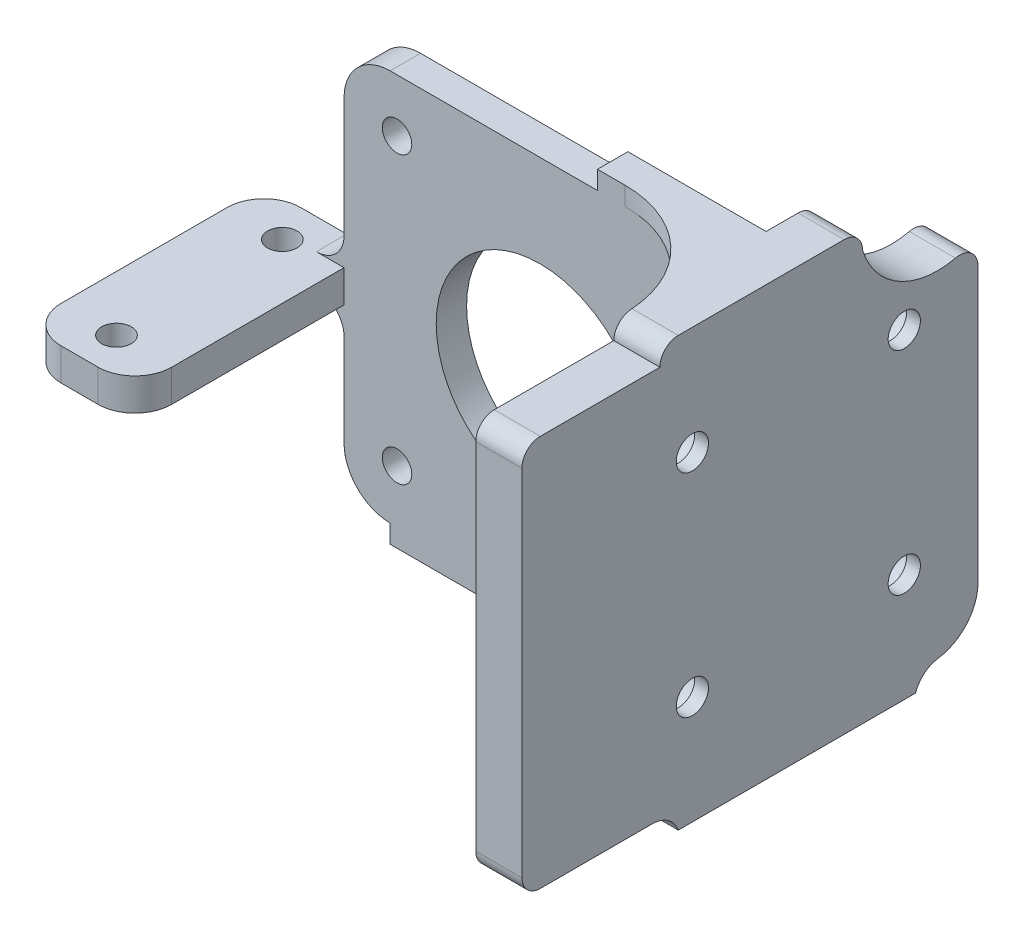
SolidWorks part; units mm, degrees
ref_plane "Alzado" through (0, 0, 0) normal (0, 0, 1) x (1, 0, 0)
ref_plane "Planta" through (0, 0, 0) normal (0, 1, 0) x (1, 0, 0)
ref_plane "Vista lateral" through (0, 0, 0) normal (1, 0, 0) x (0, 0, -1)
sketch "Croquis1" plane through (0, 0, 0) normal (1, 0, 0) x (0, 0, -1)
  line L1 (-23.5797, 14.1196) -> (18.9203, 14.1196)
  line L2 (-23.5797, 14.1196) -> (-23.5797, -28.3804)
  line L3 (-23.5797, -28.3804) -> (18.9203, -28.3804)
  line L4 (18.9203, 14.1196) -> (18.9203, -28.3804)
  dimension "D1" = 42.5
  dimension "D2" = 42.5
extrude "Saliente-Extruir1" add sketch "Croquis1" against normal blind 5
sketch "Croquis6" plane through (0, 0, -18.9203) normal (0, 0, -1) x (-1, 0, 0)
  line L4 (0, 14.1196) -> (0, -28.3804)
  line L5 (0, -28.3804) -> (5, -28.3804)
  line L6 (5, -28.3804) -> (5, 14.1196)
  line L7 (5, 14.1196) -> (0, 14.1196)
  line L8 (0, 14.1196) -> (0, -28.3804)
  line L9 (0, -28.3804) -> (5, -28.3804)
  line L10 (5, -28.3804) -> (5, 14.1196)
  line L11 (5, 14.1196) -> (0, 14.1196)
  dimension "D1" = 0
extrude "Saliente-Extruir2" add sketch "Croquis6" along normal blind 4
sketch "Croquis7" plane through (-5, 0, 0) normal (-1, 0, 0) x (0, 0, 1)
  line L0 (23.5797, -28.3804) -> (-22.9203, -28.3804) construction
  line L1 (-22.9203, 14.1196) -> (-18.9203, 14.1196)
  line L2 (-22.9203, 14.1196) -> (-22.9203, -28.3804)
  line L3 (-22.9203, -28.3804) -> (-18.9203, -28.3804)
  line L4 (-18.9203, 14.1196) -> (-18.9203, -28.3804)
  dimension "D1" = 4
extrude "Saliente-Extruir3" add sketch "Croquis7" along normal blind 42.5
sketch "Croquis8" plane through (0, 0, -18.9203) normal (0, 0, 1) x (1, 0, 0)
  line L0 (-47.5, 14.1196) -> (-41.75, 8.3696) construction
  line L1 (-47.5, -28.3804) -> (-41.75, -22.6304) construction
  line L2 (-40.6186, 7.2382) -> (-11.8814, -21.499) construction
  line L5 (-40.6186, -21.499) -> (-11.8814, 7.2382) construction
  line L7 (-40.6186, -21.499) -> (-11.8814, 7.2382) construction
  line L8 (-40.6186, 7.2382) -> (-11.8814, -21.499) construction
  line L9 (-10.75, 8.3696) -> (-5, 14.1196) construction
  line L10 (-10.75, -22.6304) -> (-5, -28.3804) construction
  circle A0 centre (-26.25, -7.1304) radius 11.25
  circle A1 centre (-41.75, 8.3696) radius 1.6
  circle A2 centre (-10.75, 8.3696) radius 1.6
  circle A3 centre (-10.75, -22.6304) radius 1.6
  circle A4 centre (-41.75, -22.6304) radius 1.6
  dimension "D1" = 22.5
  dimension "D4" = 31
  dimension "D2" = 31
  dimension "D3" = 31
extrude "Cortar-Extruir2" cut sketch "Croquis8" against normal blind 4
sketch "Croquis10" plane through (-47.5, 0, 0) normal (-1, 0, 0) x (0, 0, 1)
  line L0 (-18.9203, -28.3804) -> (-18.9203, 14.1196) construction
  line L1 (-22.9203, -28.3804) -> (-18.9203, -28.3804)
  line L3 (-22.9203, -8.3804) -> (-18.9203, -8.3804)
  line L4 (-22.9203, -8.3804) -> (-18.9203, -8.3804)
  line L5 (-22.9203, -8.3804) -> (-22.9203, -4.8804)
  line L6 (-22.9203, -4.8804) -> (-18.9203, -4.8804)
  line L7 (-18.9203, -8.3804) -> (-18.9203, -4.8804)
  line M3 (-22.9203, 14.1196) -> (-22.9203, -28.3804)
  line M5 (-18.9203, -28.3804) -> (-18.9203, 14.1196)
  dimension "D1" = 20
  dimension "D2" = 3.5
extrude "Saliente-Extruir4" add sketch "Croquis10" along normal blind 12 contours L6 L3 M3 M5
sketch "Croquis11" plane through (0, 0, -18.9203) normal (0, 0, 1) x (1, 0, 0)
  line L1 (-59.5, -4.8804) -> (-47.5, -4.8804)
  line L2 (-59.5, -4.8804) -> (-59.5, -8.3804)
  line L3 (-59.5, -8.3804) -> (-47.5, -8.3804)
  line L4 (-47.5, -4.8804) -> (-47.5, -8.3804)
extrude "Saliente-Extruir5" add sketch "Croquis11" along normal blind 22
sketch "Croquis12" plane through (0, -4.8804, 0) normal (0, 1, 0) x (1, 0, 0)
  line L0 (-59.5, 22.9203) -> (-47.5, -3.0797) construction
  line L1 (-59.5, -3.0797) -> (-47.5, 22.9203) construction
  circle A0 centre (-53.5, 18.9203) radius 1.6
  circle A1 centre (-53.5, 0.9203) radius 1.6
  point P11 (-53.5, 9.9203)
  dimension "D1" = 18
extrude "Cortar-Extruir4" cut sketch "Croquis12" against normal blind 3.5
fillet "Redondeo1" radius 5 2 edges at (-2.5, -28.3804, 23.5797) (-2.5, 14.1196, 23.5797)
fillet "Redondeo2" radius 5 2 edges at (-47.5, -28.3804, -20.9203) (-47.5, 14.1196, -20.9203)
fillet "Redondeo3" radius 4 3 edges at (-59.5, -6.6304, -22.9203) (-59.5, -6.6304, 3.0797) (-47.5, -6.6304, 3.0797)
sketch "Croquis13" plane through (0, 0, -18.9203) normal (0, 0, 1) x (1, 0, 0)
  line L7 (-47.5, -8.3804) -> (-47.5, -23.3804)
  line L8 (-42.5, -28.3804) -> (-5, -28.3804)
  line L9 (-5, -28.3804) -> (-5, 14.1196)
  line L10 (-5, 14.1196) -> (-42.5, 14.1196)
  line L11 (-47.5, 9.1196) -> (-47.5, -4.8804)
  line L13 (-47.5, -4.8804) -> (-47.5, -8.3804)
  line L14 (-47.5, -8.3804) -> (-47.5, -23.3804)
  line L15 (-42.5, -28.3804) -> (-5, -28.3804)
  line L16 (-5, -28.3804) -> (-5, 14.1196)
  line L17 (-5, 14.1196) -> (-42.5, 14.1196)
  line L18 (-47.5, 9.1196) -> (-47.5, -4.8804)
  line L20 (-47.5, -4.8804) -> (-47.5, -8.3804)
  arc A3 (-47.5, -23.3804) -> (-42.5, -28.3804) centre (-42.5, -23.3804) ccw
  arc A4 (-42.5, 14.1196) -> (-47.5, 9.1196) centre (-42.5, 9.1196) ccw
  arc A6 (-47.5, -23.3804) -> (-42.5, -28.3804) centre (-42.5, -23.3804) ccw
  arc A7 (-42.5, 14.1196) -> (-47.5, 9.1196) centre (-42.5, 9.1196) ccw
  dimension "D1" = 0
extrude "Cortar-Extruir5" cut sketch "Croquis13" against normal blind 0.7
sketch "Croquis14" plane through (0, 0, -22.9203) normal (0, 0, -1) x (-1, 0, 0)
  line L0 (0, -28.3804) -> (42.5, -28.3804) construction
  line L1 (0, 14.1196) -> (5, 14.1196)
  line L2 (0, 14.1196) -> (0, -28.3804)
  line L3 (0, -28.3804) -> (5, -28.3804)
  line L4 (5, 14.1196) -> (5, -28.3804)
  dimension "D1" = 5
extrude "Saliente-Extruir6" add sketch "Croquis14" along normal blind 18
sketch "Croquis15" plane through (0, 0, 0) normal (1, 0, 0) x (0, 0, -1)
  circle A0 centre (9.9203, 4.3696) radius 1.75
  circle A1 centre (32.9203, 4.3696) radius 1.75
  circle A2 centre (32.9203, -18.6304) radius 1.75
  circle A3 centre (9.9203, -18.6304) radius 1.75
  dimension "D1" = 23
  dimension "D2" = 23
extrude "Cortar-Extruir6" cut sketch "Croquis15" against normal blind 5
sketch "Croquis16" plane through (-5, 0, 0) normal (-1, 0, 0) x (0, 0, 1)
  circle A4 centre (-9.9203, 4.3696) radius 2.8
  circle A5 centre (-9.9203, -18.6304) radius 2.8
extrude "Cortar-Extruir7" cut sketch "Croquis16" against normal blind 3.5
sketch "Croquis17" plane through (-5, 0, 0) normal (-1, 0, 0) x (0, 0, 1)
  circle A4 centre (-32.9203, 4.3696) radius 2.8
  circle A5 centre (-32.9203, -18.6304) radius 2.8
extrude "Cortar-Extruir8" cut sketch "Croquis17" against normal blind 3.5
fillet "Redondeo5" radius 5 2 edges at (-2.5, -28.3804, -40.9203) (-2.5, 14.1196, -40.9203)
sketch "Croquis18" plane through (0, -8.3804, 0) normal (0, -1, 0) x (1, 0, 0)
  line L5 (-59.5, -0.9203) -> (-59.5, -18.9203)
  line L6 (-55.5, -22.9203) -> (-47.5, -22.9203)
  line L7 (-47.5, -22.9203) -> (-47.5, -19.6203)
  line L8 (-47.5, -19.6203) -> (-47.5, -0.9203)
  line L9 (-51.5, 3.0797) -> (-55.5, 3.0797)
  line L10 (-59.5, -0.9203) -> (-59.5, -18.9203)
  line L11 (-55.5, -22.9203) -> (-47.5, -22.9203)
  line L12 (-47.5, -22.9203) -> (-47.5, -19.6203)
  line L13 (-47.5, -19.6203) -> (-47.5, -0.9203)
  line L14 (-51.5, 3.0797) -> (-55.5, 3.0797)
  circle A0 centre (-53.5, -0.9203) radius 1.6 construction
  circle A1 centre (-53.5, -18.9203) radius 1.6 construction
  circle A2 centre (-53.5, -0.9203) radius 1.6
  arc A3 (-59.5, -18.9203) -> (-55.5, -22.9203) centre (-55.5, -18.9203) ccw
  arc A4 (-47.5, -0.9203) -> (-51.5, 3.0797) centre (-51.5, -0.9203) ccw
  arc A5 (-55.5, 3.0797) -> (-59.5, -0.9203) centre (-55.5, -0.9203) ccw
  arc A6 (-59.5, -18.9203) -> (-55.5, -22.9203) centre (-55.5, -18.9203) ccw
  arc A7 (-47.5, -0.9203) -> (-51.5, 3.0797) centre (-51.5, -0.9203) ccw
  arc A8 (-55.5, 3.0797) -> (-59.5, -0.9203) centre (-55.5, -0.9203) ccw
  circle A9 centre (-53.5, -18.9203) radius 1.6
  dimension "D1" = 0
extrude "Saliente-Extruir8" add sketch "Croquis18" along normal blind 2
sketch "Croquis19" plane through (0, -4.8804, 0) normal (0, 1, 0) x (1, 0, 0)
  line L0 (-51.5, -3.0797) -> (-55.5, -3.0797) construction
  line L1 (-59.5, 18.9203) -> (-59.5, 0.9203) construction
  line L2 (-55.5, 22.9203) -> (-47.5, 22.9203) construction
  line L3 (-47.5, 22.9203) -> (-47.5, 19.6203) construction
  line L4 (-47.5, 0.9203) -> (-47.5, 19.6203) construction
  line L5 (-51.5, -3.0797) -> (-55.5, -3.0797)
  line L6 (-59.5, 18.9203) -> (-59.5, 0.9203)
  line L7 (-55.5, 22.9203) -> (-47.5, 22.9203)
  line L8 (-47.5, 22.9203) -> (-47.5, 19.6203)
  line L9 (-47.5, 0.9203) -> (-47.5, 19.6203)
  arc A0 (-51.5, -3.0797) -> (-47.5, 0.9203) centre (-51.5, 0.9203) ccw construction
  arc A1 (-59.5, 0.9203) -> (-55.5, -3.0797) centre (-55.5, 0.9203) ccw construction
  arc A2 (-55.5, 22.9203) -> (-59.5, 18.9203) centre (-55.5, 18.9203) ccw construction
  circle A3 centre (-53.5, 18.9203) radius 1.6 construction
  circle A4 centre (-53.5, 0.9203) radius 1.6 construction
  arc A5 (-51.5, -3.0797) -> (-47.5, 0.9203) centre (-51.5, 0.9203) ccw
  arc A6 (-59.5, 0.9203) -> (-55.5, -3.0797) centre (-55.5, 0.9203) ccw
  arc A7 (-55.5, 22.9203) -> (-59.5, 18.9203) centre (-55.5, 18.9203) ccw
  circle A8 centre (-53.5, 18.9203) radius 1.6
  circle A9 centre (-53.5, 0.9203) radius 1.6
extrude "Cortar-Extruir9" cut sketch "Croquis19" against normal blind 2
fillet "Redondeo7" radius 3 1 edges at (-47.5, -6.8804, -21.2703)
fillet "Redondeo8" radius 3 1 edges at (-47.5, -10.3804, -21.2703)
sketch "Croquis20" plane through (0, -28.3804, 0) normal (0, -1, 0) x (1, 0, 0)
  line L8 (-5, -22.9203) -> (-5, -35.9203)
  line L9 (-5, -35.9203) -> (0, -35.9203)
  line L10 (0, -35.9203) -> (0, 18.5797)
  line L11 (0, 18.5797) -> (-5, 18.5797)
  line L12 (-5, 18.5797) -> (-5, -19.6203)
  line L13 (-5, -19.6203) -> (-42.5, -19.6203)
  line L14 (-42.5, -19.6203) -> (-42.5, -22.9203)
  line L15 (-42.5, -22.9203) -> (-5, -22.9203)
  line L16 (-5, -22.9203) -> (-5, -35.9203)
  line L17 (-5, -35.9203) -> (0, -35.9203)
  line L18 (0, -35.9203) -> (0, 18.5797)
  line L20 (-5, 18.5797) -> (-5, -19.6203)
  line L21 (-5, -19.6203) -> (-42.5, -19.6203)
  line L22 (-42.5, -19.6203) -> (-42.5, -22.9203)
  line L23 (-42.5, -22.9203) -> (-5, -22.9203)
  line L25 (0, 18.5797) -> (-5, 18.5797)
  dimension "D1" = 0
extrude "Saliente-Extruir9" add sketch "Croquis20" along normal blind 2
sketch "Croquis21" plane through (0, -30.3804, 0) normal (0, -1, 0) x (1, 0, 0)
  line L0 (-42.5, -22.9203) -> (-5, -22.9203) construction
  line L9 (-5, -35.9203) -> (-5, -22.9203)
  line L10 (-5, -22.9203) -> (-16.2298, -22.9203)
  line L11 (-5, 18.5797) -> (-5, -19.6203) construction
  line L12 (-5, -19.6203) -> (-42.5, -19.6203) construction
  line L13 (-5, -19.6203) -> (-16.2298, -19.6203)
  line L14 (-5, -19.6203) -> (-5, -4.3631)
  arc A0 (-5, -35.9203) -> (-16.2298, -22.9203) centre (-17.1149, -35.0352) ccw
  arc A1 (-5, -4.3631) -> (-16.2298, -19.6203) centre (-18.2435, -6.3768) cw
  line M9 (-42.5, -22.9203) -> (-5, -22.9203)
  line M10 (-5, -22.9203) -> (-5, -35.9203)
  line M15 (-5, -19.6203) -> (-42.5, -19.6203)
extrude "Saliente-Extruir10" add sketch "Croquis21" against normal blind 2 contours L14 A1 M15 | A0 M10 M9
sketch "Croquis22" plane through (-5, 0, 0) normal (-1, 0, 0) x (0, 0, 1)
  line L1 (-8.3905, -30.3804) -> (18.5797, -30.3804)
  line L2 (-8.3905, -30.3804) -> (-8.3905, -28.3804)
  line L3 (-8.3905, -28.3804) -> (18.5797, -28.3804)
  line L4 (18.5797, -30.3804) -> (18.5797, -28.3804)
extrude "Cortar-Extruir10" cut sketch "Croquis22" against normal blind 5
sketch "Croquis23" plane through (-5, 0, 0) normal (-1, 0, 0) x (0, 0, 1)
  line L1 (-35.9203, -28.3804) -> (-34.1501, -28.3804)
  line L2 (-35.9203, -28.3804) -> (-35.9203, -30.3804)
  line L3 (-35.9203, -30.3804) -> (-34.1501, -30.3804)
  line L4 (-34.1501, -28.3804) -> (-34.1501, -30.3804)
extrude "Cortar-Extruir11" cut sketch "Croquis23" against normal blind 5
fillet "Redondeo9" radius 3 2 edges at (-2.5, -28.3804, -34.1501) (-2.5, -28.3804, -8.3905)
sketch "Croquis24" plane through (0, 0, 0) normal (1, 0, 0) x (0, 0, -1)
  line L0 (-18.5797, -28.3804) -> (5.562, -28.3804) construction
  line L1 (-23.5797, 9.1196) -> (-23.5797, -23.3804) construction
  line L2 (35.9203, 14.1196) -> (-18.5797, 14.1196) construction
  line L3 (-18.5797, -28.3804) -> (-8.5797, -28.3804)
  line L4 (-23.5797, 9.1196) -> (-23.5797, -23.3804)
  line L5 (-8.5797, 14.1196) -> (-18.5797, 14.1196)
  line L6 (-8.5797, 14.1196) -> (-8.5797, -28.3804)
  line L7 (40.9203, 9.1196) -> (40.9203, -23.3804) construction
  line L8 (-8.5797, 14.1196) -> (-18.5797, 14.1196)
  line L9 (35.9203, 14.1196) -> (28.3962, 14.1196)
  arc A0 (-23.5797, -23.3804) -> (-18.5797, -28.3804) centre (-18.5797, -23.3804) ccw construction
  arc A1 (-18.5797, 14.1196) -> (-23.5797, 9.1196) centre (-18.5797, 9.1196) ccw construction
  arc A2 (-23.5797, -23.3804) -> (-18.5797, -28.3804) centre (-18.5797, -23.3804) ccw
  arc A3 (-18.5797, 14.1196) -> (-23.5797, 9.1196) centre (-18.5797, 9.1196) ccw
  arc A5 (28.3962, 14.1196) -> (40.9152, 9.344) centre (36.5203, 16.6196) ccw
  arc A6 (40.9203, 9.1196) -> (35.9203, 14.1196) centre (35.9203, 9.1196) ccw construction
  arc A7 (40.9152, 9.344) -> (35.9203, 14.1196) centre (35.9203, 9.1196) ccw
  point P12 (0, 0)
  point P13 (0, 0)
  point P14 (35.8515, 16.6196)
  dimension "D2" = 17
  dimension "D1" = 15
  dimension "D3" = 2.5
  dimension "D4" = 4.4
extrude "Cortar-Extruir12" cut sketch "Croquis24" along direction (1, 0, 0) on the side against the normal up to surface (5 mm away) contours L3 L6 L5 A3 L4 A2 | A5 A7 L9
fillet "Redondeo10" radius 2 3 edges at (-2.5, 9.344, -40.9152) (-2.5, -28.3804, 8.5797) (-2.5, 14.1196, 8.5797)
sketch "Croquis25" plane through (0, 14.1196, 0) normal (0, 1, 0) x (1, 0, 0)
  line L0 (-20, 22.9203) -> (-20, 19.6203)
  line L1 (0, 6.3962) -> (-5, 6.3962)
  line L8 (-5, 19.6203) -> (-5, -6.5797)
  line L9 (-5, -6.5797) -> (0, -6.5797)
  line L10 (0, -6.5797) -> (0, 28.3962)
  line L11 (0, 28.3962) -> (-5, 28.3962)
  line L12 (-5, 28.3962) -> (-5, 22.9203)
  line L13 (-5, 22.9203) -> (-42.5, 22.9203)
  line L14 (-42.5, 22.9203) -> (-42.5, 19.6203)
  line L15 (-42.5, 19.6203) -> (-5, 19.6203)
  line L16 (-5, 7.6203) -> (-5, 6.3962)
  line L18 (0, 6.3962) -> (0, 28.3962)
  line L19 (0, 28.3962) -> (-5, 28.3962)
  line L20 (-5, 28.3962) -> (-5, 22.9203)
  line L21 (-5, 22.9203) -> (-20, 22.9203)
  line L23 (-20, 19.6203) -> (-17, 19.6203)
  arc A0 (-5, 7.6203) -> (-17, 19.6203) centre (-17, 7.6203) ccw
  dimension "D2" = 12
  dimension "D3" = 22
  dimension "D4" = 15
  dimension "D1" = 0
extrude "Saliente-Extruir11" add sketch "Croquis25" along normal blind 2
fillet "Redondeo11" radius 2 2 edges at (-2.5, 16.1196, -28.3962) (-2.5, 16.1196, -6.3962)
